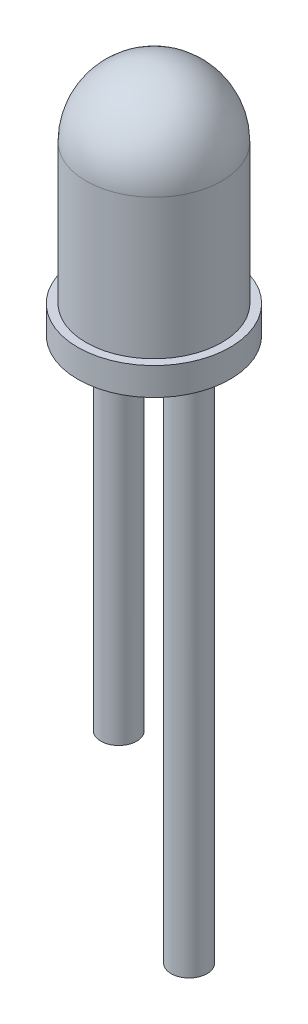
SolidWorks part; units mm, degrees
ref_plane "Alzado" through (0, 0, 0) normal (0, 0, 1) x (1, 0, 0)
ref_plane "Planta" through (0, 0, 0) normal (0, 1, 0) x (1, 0, 0)
ref_plane "Vista lateral" through (0, 0, 0) normal (1, 0, 0) x (0, 0, -1)
sketch "Croquis1" plane through (0, 0, 0) normal (0, 1, 0) x (1, 0, 0)
  circle A0 centre (0, 0) radius 2.75
  dimension "D1" = 5.5
extrude "Saliente-Extruir1" add sketch "Croquis1" along normal blind 1
sketch "Croquis2" plane through (0, 1, 0) normal (0, 1, 0) x (1, 0, 0)
  circle A0 centre (0, 0) radius 2.45
  dimension "D1" = 4.9
extrude "Saliente-Extruir2" add sketch "Croquis2" along normal blind 5.05 contours A0
dome "Cúpula1" faces to dome 1 distance 2.45 reverse direction no elliptical dome no face at (0, 6.05, 2.45) parameters "D1"=2.45
sketch "Croquis3" plane through (0, 0, 0) normal (0, -1, 0) x (1, 0, 0)
  line L0 (0, -3.025) -> (0, 3.025) construction
  circle A0 centre (-1.2052, 0) radius 0.25
  circle A1 centre (1.2052, 0) radius 0.25
  dimension "D1" = 0.5
extrude "Saliente-Extruir3" add sketch "Croquis3" along normal blind 16 contours A0
sketch "Croquis5" plane through (0, 0, 0) normal (0, -1, 0) x (1, 0, 0)
  circle A1 centre (1.2052, 0) radius 0.25
  circle A2 centre (1.2052, 0) radius 0.25
  dimension "D1" = 0
extrude "Saliente-Extruir5" add sketch "Croquis5" along normal blind 17
ref_plane "Plane1" through (0, 6.05, 0) normal (0, -1, 0) x (-1, 0, 0)
sketch "Sketch1" plane through (0, 6.05, 0) normal (0, -1, 0) x (-1, 0, 0)
  point P0 (0, 0)
sketch "Sketch2" plane through (0, -16, 0) normal (0, -1, 0) x (1, 0, 0)
  circle A0 centre (-1.2052, 0) radius 0.25
  circle A1 centre (1.2052, 0) radius 0.25
  circle A2 centre (1.2052, 0) radius 0.25 construction
  circle A3 centre (-1.2052, 0) radius 0.25 construction
extrude "Cut-Extrude1" cut sketch "Sketch2" against normal up to surface (16 mm away) up to face at (1.2052, 0, 0.25)
sketch "Sketch3" plane through (0, -17, 0) normal (0, -1, 0) x (1, 0, 0)
  circle A1 centre (1.2052, 0) radius 0.25
  circle A2 centre (1.2052, 0) radius 0.25
  dimension "D1" = 0
extrude "Cut-Extrude2" cut sketch "Sketch3" against normal blind 10
sketch "Sketch4" plane through (0, 0, 0) normal (0, -1, 0) x (1, 0, 0)
  line L0 (1.27, 0) -> (-1.27, 0) construction
  circle A0 centre (1.27, 0) radius 0.65
  circle A1 centre (-1.27, 0) radius 0.65
  point P4 (0, 0)
  dimension "D2" = 1.3
  dimension "D1" = 2.54
extrude "Boss-Extrude1" add sketch "Sketch4" along normal blind 13
sketch "Sketch5" plane through (0, -13, 0) normal (0, -1, 0) x (1, 0, 0)
  circle A1 centre (1.27, 0) radius 0.65
  circle A2 centre (1.27, 0) radius 0.65
  dimension "D1" = 0
extrude "Boss-Extrude2" add sketch "Sketch5" along normal blind 6
